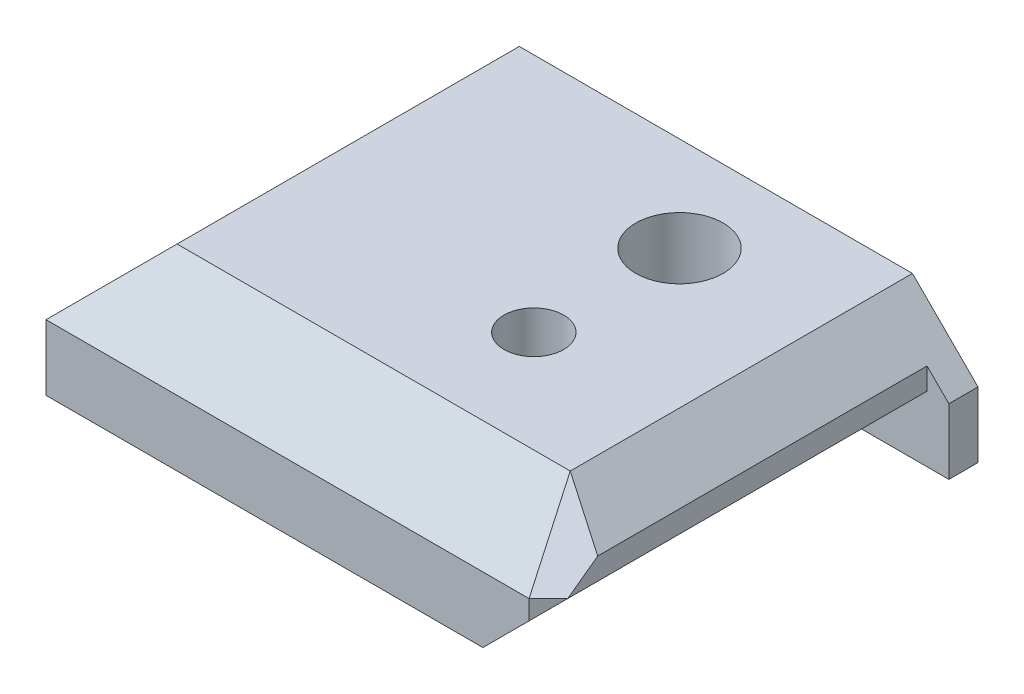
SolidWorks part; units mm, degrees
ref_plane "Front Plane" through (0, 0, 0) normal (0, 0, 1) x (1, 0, 0)
ref_plane "Top Plane" through (0, 0, 0) normal (0, 1, 0) x (1, 0, 0)
ref_plane "Right Plane" through (0, 0, 0) normal (1, 0, 0) x (0, 0, -1)
sketch "Sketch1" plane through (0, 0, 0) normal (0, 0, 1) x (1, 0, 0)
  line L0 (0, 0) -> (0, 9)
  line L1 (0, 9) -> (36, 9)
  line L2 (36, 9) -> (36, 0)
  line L3 (55, 0) -> (-55, 0) construction
  line L4 (36, 0) -> (0, 0)
extrude "Boss-Extrude1" add sketch "Sketch1" along normal blind 28
ref_plane "Plane1" through (0, 4.5, 0) normal (0, -1, 0) x (-1, 0, 0)
sketch "Sketch2" plane through (0, 0, 0) normal (0, 0, 1) x (1, 0, 0)
  line L0 (0, 4.5) -> (4.5, 9)
  line L1 (0, 9) -> (0, 0) construction
  line L2 (36, 9) -> (0, 9) construction
  line L3 (0, 4.5) -> (0, 9)
  line L4 (0, 9) -> (4.5, 9)
  line L5 (18, 10.7859) -> (18, -2.0026) construction
  line L6 (36, 4.5) -> (31.5, 9)
  line L7 (36, 4.5) -> (36, 9)
  line L8 (36, 9) -> (31.5, 9)
extrude "Cut-Extrude1" cut sketch "Sketch2" along normal blind 28
sketch "Sketch3" plane through (0, 0, 0) normal (1, 0, 0) x (0, 0, -1)
  line L0 (-28, 4.5) -> (-23.5, 9)
  line L1 (-28, 4.5) -> (0, 4.5) construction
  line L2 (-28, 0) -> (-28, 4.5) construction
  line L3 (-28, 9) -> (0, 9) construction
  line L4 (-28, 4.5) -> (-28, 9)
  line L5 (-28, 9) -> (-23.5, 9)
extrude "Cut-Extrude2" cut sketch "Sketch3" along normal blind 36
ref_plane "Plane2" through (32, 0, 32) normal (0.7071, 0, 0.7071) x (0, 1, 0)
sketch "Sketch5" plane through (32, 0, 32) normal (0.7071, 0, 0.7071) x (0, 1, 0)
  line L0 (0, -15.4) -> (0, 15.4) construction
  line L1 (0, 1.8738) -> (11.4404, 1.8738)
  line L2 (0, 1.8738) -> (0, -13.7452)
  line L3 (0, -13.7452) -> (11.4404, -13.7452)
  line L4 (11.4404, 1.8738) -> (11.4404, -13.7452)
extrude "Cut-Extrude4" cut sketch "Sketch5" against normal blind 2
ref_plane "Plane3" through (4, 0, -4) normal (-0.7071, 0, 0.7071) x (0.5774, -0.5774, 0.5774)
sketch "Sketch6" plane through (4, 0, -4) normal (-0.7071, 0, 0.7071) x (0.5774, -0.5774, 0.5774)
  line L0 (26.5581, 29.8021) -> (32.7193, 28.6474)
  line L1 (32.7193, 28.6474) -> (30.1986, 32.2123)
  line L2 (30.1986, 32.2123) -> (26.5581, 29.8021)
extrude "Cut-Extrude5" cut sketch "Sketch6" against normal blind 2 and the other way blind 2
sketch "Sketch7" plane through (0, 0, 0) normal (0, 0, 1) x (1, 0, 0)
  line L0 (0, 0) -> (5, 0) construction
  line L1 (15.4226, 0) -> (-15.4226, 0) construction
  line L2 (5, 0) -> (5, 3)
  line L3 (5, 0) -> (13.8116, 0)
  line L4 (13.8116, 0) -> (13.8116, 3)
  line L5 (5, 3) -> (5.7071, 3.7071)
  line L9 (13.8116, 3) -> (13.1045, 3.7071)
  line L10 (5.7071, 3.7071) -> (13.1045, 3.7071)
extrude "Cut-Extrude6" cut sketch "Sketch7" along normal blind 26
ref_plane "Plane5" through (0, 0, 28) normal (0, 0, 1) x (1, 0, 0)
sketch "Sketch8" plane through (0, 0, 28) normal (0, 0, 1) x (1, 0, 0)
  line L1 (15.4, 0) -> (-15.4, 0) construction
  line L2 (36, 0) -> (36, 4.5) construction
  line L3 (36, 0) -> (30, 0)
  line L5 (31.5, 9) -> (36, 4.5) construction
  line L8 (34.5, 4.5) -> (34.5, 6)
  line L9 (33.1716, 4.5) -> (36, 4.5) construction
  line L10 (34.5, 6) -> (36, 6)
  line L11 (36, 6) -> (36, 0)
  line L12 (34.5, 4.5) -> (30, 0)
extrude "Cut-Extrude7" cut sketch "Sketch8" against normal blind 26
sketch "Sketch9" plane through (0, 0, 0) normal (0, 1, 0) x (1, 0, 0)
  line L0 (0, -6.5) -> (19, -6.5) construction
  line L1 (0, -4.95) -> (0, 4.95) construction
  line L2 (5.7775, 0) -> (5.7775, -6.5) construction
  line L3 (-6.8862, 0) -> (6.8862, 0) construction
  line L4 (19, -6.5) -> (22, -6.5)
  circle A0 centre (22, -6.5) radius 3
sketch "Sketch10" plane through (0, 9, 0) normal (0, 1, 0) x (1, 0, 0)
  circle A0 centre (22, -6.5) radius 3
extrude "Cut-Extrude8" cut sketch "Sketch10" against normal blind 7
sketch "Sketch11" plane through (0, 2, 0) normal (0, 1, 0) x (1, 0, 0)
  circle A0 centre (22, -6.5) radius 1.5
extrude "Cut-Extrude9" cut sketch "Sketch11" against normal up to surface (2 mm away) up to face at (16.9623, 0, 11.2)
sketch "Sketch12" plane through (0, 0, 0) normal (0, 1, 0) x (1, 0, 0)
  line L0 (22, -8) -> (22, -15) construction
  line L1 (22, -15) -> (22, -16.5)
  circle A0 centre (22, -6.5) radius 1.5 construction
  circle A1 centre (22, -16.5) radius 1.5
extrude "Cut-Extrude10" cut sketch "Sketch12" along normal up to surface (9 mm away) contours A1 region at (20.9693, 0, 17.5307) up to face at (22, 9, 9.5)
sketch "Sketch13" plane through (0, 9, 0) normal (0, 1, 0) x (1, 0, 0)
  line L0 (22, -16.5) -> (19.95, -16.5) construction
  circle A0 centre (22, -16.5) radius 2.05
extrude "Cut-Extrude11" cut sketch "Sketch13" against normal blind 7
